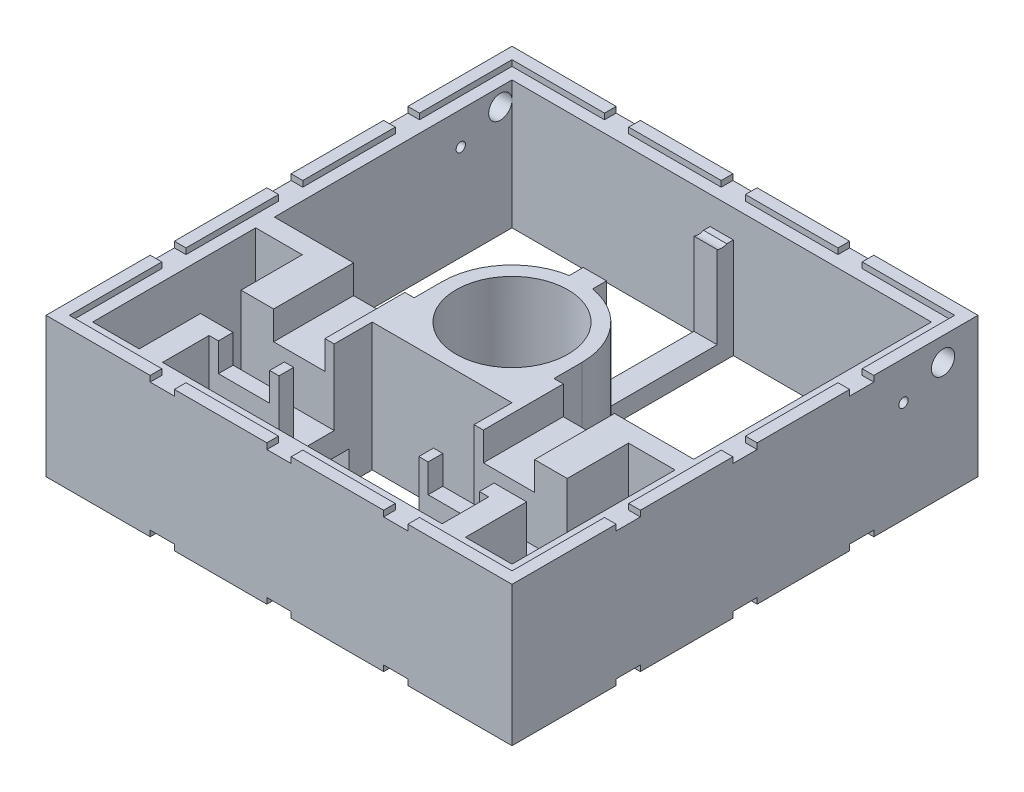
SolidWorks part; units mm, degrees
material "Polyethylene Cross-Linked"
ref_plane "Front Plane" through (0, 0, 0) normal (0, 0, 1) x (1, 0, 0)
ref_plane "Top Plane" through (0, 0, 0) normal (0, 1, 0) x (1, 0, 0)
ref_plane "Right Plane" through (0, 0, 0) normal (1, 0, 0) x (0, 0, -1)
sketch "Sketch1" plane through (0, 0, 0) normal (0, 1, 0) x (1, 0, 0)
  line L0 (57.15, 57.15) -> (-57.15, 57.15)
  line L5 (63.5, -63.5) -> (-63.5, -63.5)
  line L6 (63.5, -63.5) -> (63.5, 63.5)
  line L7 (63.5, 63.5) -> (-63.5, 63.5)
  line L8 (-63.5, -63.5) -> (-63.5, 63.5)
  line L9 (63.5, -63.5) -> (-63.5, 63.5) construction
  line L10 (63.5, 63.5) -> (-63.5, -63.5) construction
  line L11 (-57.15, -57.15) -> (-57.15, 57.15)
  line L12 (57.15, -57.15) -> (-57.15, -57.15)
  line L13 (57.15, -57.15) -> (57.15, 57.15)
  point P0 (0, 0)
  dimension "D2" = 6.35
  dimension "D1" = 127
extrude "Boss-Extrude1" add sketch "Sketch1" along normal blind 38.1
sketch "Sketch2" plane through (0, 0, 0) normal (0, 1, 0) x (1, 0, 0)
  line L0 (-57.15, -12.7) -> (-57.15, -7.62)
  line L2 (-57.15, -7.62) -> (-19.05, -7.62)
  line L3 (-19.05, -7.62) -> (-19.05, -44.45)
  line L7 (-44.45, -57.15) -> (-44.45, -12.7)
  line L8 (-44.45, -12.7) -> (-57.15, -12.7)
  line L9 (0, -76.0173) -> (0, 81.3082) construction
  line L12 (44.45, -57.15) -> (44.45, -12.7)
  line L13 (44.45, -12.7) -> (57.15, -12.7)
  line L14 (57.15, -7.62) -> (19.05, -7.62)
  line L15 (19.05, -7.62) -> (19.05, -44.45)
  line L16 (-19.05, -19.05) -> (19.05, -19.05)
  line L17 (-3.175, 57.15) -> (-3.175, 18.7836)
  line L19 (3.175, 57.15) -> (3.175, 18.7836)
  line L20 (3.175, 57.15) -> (-3.175, 57.15)
  line L21 (57.15, -7.62) -> (57.15, -12.7)
  line L24 (-19.05, -44.45) -> (-38.1, -44.45)
  line L27 (-38.1, -44.45) -> (-38.1, -57.15)
  line L28 (19.05, -44.45) -> (38.1, -44.45)
  line L29 (38.1, -44.45) -> (38.1, -57.15)
  line L30 (-19.05, 0) -> (-19.05, -7.62)
  line L31 (19.05, 0) -> (19.05, -7.62)
  line L32 (-44.45, -57.15) -> (-38.1, -57.15)
  line L33 (44.45, -57.15) -> (38.1, -57.15)
  line L34 (-57.15, -57.15) -> (57.15, -57.15) construction
  line L35 (-57.15, 57.15) -> (-57.15, -57.15) construction
  line L36 (57.15, 57.15) -> (-57.15, 57.15) construction
  circle A4 centre (0, 0) radius 19.05
  point P27 (0, -19.05)
  dimension "D5" = 6.35
  dimension "D7" = 38.1
  dimension "D1" = 44.45
  dimension "D2" = 5.08
  dimension "D3" = 12.7
  dimension "D4" = 25.4
  dimension "D6" = 6.35
  dimension "D8" = 12.7
extrude "Boss-Extrude2" add sketch "Sketch2" along normal up to surface (38.1 mm away) contours A4 L9 | L9 A4 | L9 A4 L19 L20 | A4 L9 L20 L17 | L7 L32 L27 L24 L3 L2 L0 L8 | L33 L12 L13 L21 L14 L15 L28 L29 | A4 L30 L3 L16 | A4 L16 L15 L31 region at (-33.5981, 0, 26.9354) region at (-14.7948, 0, 14.7948) region at (-8.0851, 0, 0) region at (14.7948, 0, 14.7948) region at (8.0851, 0, 0) region at (-1.5893, 0, -38.0556) region at (1.5893, 0, -38.0556) region at (33.5981, 0, 26.9354) up to face at (0, 38.1, 0)
sketch "Sketch3" plane through (88.9, 38.1, 0) normal (0, -1, 0) x (-1, 0, 0)
  circle A0 centre (88.9, 0) radius 15.24
  arc A1 (85.725, 18.7836) -> (69.85, 0) centre (88.9, 0) ccw construction
  dimension "D1" = 30.48
extrude "Cut-Extrude1" cut sketch "Sketch3" along normal offset from surface (34.29 mm away) 3.81 up to face at (50.8, 0, 34.925)
sketch "Sketch4" plane through (44.45, 0, 0) normal (1, 0, 0) x (0, 0, -1)
  line L0 (-34.925, 38.1) -> (-34.925, 0) construction
  line L3 (-40.4495, 21.59) -> (-40.4495, 16.0655)
  line L4 (-40.4495, 21.59) -> (-40.4495, 38.1)
  line L5 (-40.4495, 38.1) -> (-29.4005, 38.1)
  line L6 (-29.4005, 38.1) -> (-29.4005, 21.59)
  line L7 (-12.7, 38.1) -> (-57.15, 38.1) construction
  line L8 (-40.4495, 16.0655) -> (-29.4005, 16.0655)
  line L9 (-29.4005, 16.0655) -> (-29.4005, 21.59)
  circle A0 centre (-34.925, 21.59) radius 5.5245 construction
  dimension "D1" = 11.049
  dimension "D2" = 16.51
extrude "Cut-Extrude2" cut sketch "Sketch4" against normal up to surface (25.4 mm away) contours L4 L6 region at (44.45, 27.0828, 34.925) up to face at (19.05, 19.05, 31.75)
sketch "Sketch5" plane through (-44.45, 0, 0) normal (-1, 0, 0) x (0, 0, 1)
  line L3 (40.4495, 21.59) -> (40.4495, 38.1)
  line L4 (40.4495, 38.1) -> (29.4005, 38.1)
  line L5 (29.4005, 38.1) -> (29.4005, 21.59)
  line L6 (40.4495, 21.59) -> (40.4495, 38.1)
  line L7 (40.4495, 38.1) -> (29.4005, 38.1)
  line L8 (29.4005, 38.1) -> (29.4005, 21.59)
  line L12 (40.4495, 16.0655) -> (40.4495, 21.59)
  line L13 (40.4495, 16.0655) -> (40.4495, 21.59)
  line L14 (29.4005, 16.0655) -> (40.4495, 16.0655)
  line L15 (29.4005, 16.0655) -> (40.4495, 16.0655)
  line L16 (29.4005, 21.59) -> (29.4005, 16.0655)
  line L17 (29.4005, 21.59) -> (29.4005, 16.0655)
  dimension "D1" = 0
extrude "Cut-Extrude3" cut sketch "Sketch5" against normal up to next
sketch "Sketch8" plane through (0, 38.1, 0) normal (0, 1, 0) x (1, 0, 0)
  line L0 (-60.325, 60.325) -> (-35.1155, 60.325)
  line L1 (-35.1155, 60.325) -> (-35.1155, 63.5)
  line L2 (63.5, 63.5) -> (-63.5, 63.5) construction
  line L3 (-35.1155, 63.5) -> (-28.5115, 63.5)
  line L4 (-28.5115, 63.5) -> (-28.5115, 60.325)
  line L5 (-28.5115, 60.325) -> (-3.302, 60.325)
  line L6 (-60.325, 60.325) -> (-60.325, 35.1155)
  line L7 (-60.325, 35.1155) -> (-63.5, 35.1155)
  line L8 (-63.5, 63.5) -> (-63.5, -63.5) construction
  line L9 (-63.5, 35.1155) -> (-63.5, 28.5115)
  line L10 (-63.5, 28.5115) -> (-60.325, 28.5115)
  line L11 (-60.325, 28.5115) -> (-60.325, 3.302)
  line L12 (-60.325, 3.302) -> (-63.5, 3.302)
  line L13 (-63.5, 3.302) -> (-63.5, -3.302)
  line L14 (-63.5, -3.302) -> (-60.325, -3.302)
  line L15 (-60.325, -3.302) -> (-60.325, -28.5115)
  line L16 (-60.325, -28.5115) -> (-63.5, -28.5115)
  line L17 (-63.5, -28.5115) -> (-63.5, -35.1155)
  line L18 (-63.5, -35.1155) -> (-60.325, -35.1155)
  line L19 (-60.325, -35.1155) -> (-60.325, -60.325)
  line L20 (-60.325, -60.325) -> (-35.1155, -60.325)
  line L21 (-35.1155, -60.325) -> (-35.1155, -63.5)
  line L22 (-63.5, -63.5) -> (63.5, -63.5) construction
  line L23 (-35.1155, -63.5) -> (-28.5115, -63.5)
  line L24 (-28.5115, -63.5) -> (-28.5115, -60.325)
  line L25 (-28.5115, -60.325) -> (-3.302, -60.325)
  line L26 (-3.302, 60.325) -> (-3.302, 63.5)
  line L27 (3.302, -60.325) -> (3.302, -63.5)
  line L28 (-3.302, 63.5) -> (3.302, 63.5)
  line L29 (-3.302, -60.325) -> (-3.302, -63.5)
  line L30 (-3.302, -63.5) -> (3.302, -63.5)
  line L31 (0, 63.5) -> (0, -63.5) construction
  line L32 (28.5115, -60.325) -> (3.302, -60.325)
  line L33 (28.5115, -63.5) -> (28.5115, -60.325)
  line L34 (35.1155, -63.5) -> (28.5115, -63.5)
  line L35 (35.1155, -60.325) -> (35.1155, -63.5)
  line L36 (60.325, -60.325) -> (35.1155, -60.325)
  line L37 (60.325, -35.1155) -> (60.325, -60.325)
  line L38 (63.5, -35.1155) -> (60.325, -35.1155)
  line L39 (63.5, -28.5115) -> (63.5, -35.1155)
  line L40 (60.325, -28.5115) -> (63.5, -28.5115)
  line L41 (60.325, -3.302) -> (60.325, -28.5115)
  line L42 (63.5, -3.302) -> (60.325, -3.302)
  line L43 (63.5, 3.302) -> (63.5, -3.302)
  line L44 (60.325, 3.302) -> (63.5, 3.302)
  line L45 (60.325, 28.5115) -> (60.325, 3.302)
  line L46 (63.5, 28.5115) -> (60.325, 28.5115)
  line L47 (63.5, 35.1155) -> (63.5, 28.5115)
  line L48 (60.325, 35.1155) -> (63.5, 35.1155)
  line L49 (60.325, 60.325) -> (60.325, 35.1155)
  line L50 (60.325, 60.325) -> (35.1155, 60.325)
  line L51 (35.1155, 60.325) -> (35.1155, 63.5)
  line L52 (35.1155, 63.5) -> (28.5115, 63.5)
  line L53 (28.5115, 63.5) -> (28.5115, 60.325)
  line L54 (28.5115, 60.325) -> (3.302, 60.325)
  line L55 (3.302, 60.325) -> (3.302, 63.5)
  point P41 (-63.5, 0)
  dimension "D1" = 3.175
  dimension "D2" = 3.175
  dimension "D3" = 3.175
  dimension "D4" = 6.604
  dimension "D6" = 3.302
extrude "Cut-Extrude6" cut sketch "Sketch8" against normal blind 1.5875
sketch "Sketch9" plane through (3.175, 0, 0) normal (1, 0, 0) x (0, 0, -1)
  line L0 (22.5936, 36.5125) -> (22.5936, 6.35)
  line L1 (18.7836, 36.5125) -> (57.15, 36.5125) construction
  line L2 (22.5936, 6.35) -> (52.7561, 6.35)
  line L4 (22.5936, 36.5125) -> (53.34, 36.5125)
  line L5 (18.7836, 36.5125) -> (18.7836, 0) construction
  line L6 (57.15, 0) -> (18.7836, 0) construction
  line L7 (53.34, 36.5125) -> (57.15, 36.5125)
  line L8 (57.15, 36.5125) -> (57.15, 28.8925)
  line L9 (57.15, 28.8925) -> (52.7561, 28.8925)
  line L10 (52.7561, 28.8925) -> (52.7561, 6.35)
  point P4 (37.9668, 36.5125)
  dimension "D1" = 3.81
  dimension "D2" = 6.35
  dimension "D3" = 7.62
extrude "Cut-Extrude7" cut sketch "Sketch9" against normal up to next
sketch "Sketch10" plane through (0, 0, 7.62) normal (0, 0, -1) x (-1, 0, 0)
  line L0 (21.59, 36.5125) -> (21.59, 28.7655)
  line L1 (21.59, 28.7655) -> (35.56, 28.7655)
  line L2 (35.56, 28.7655) -> (35.56, 36.5125)
  line L3 (28.5115, 36.5125) -> (35.1155, 36.5125) construction
  line L4 (35.56, 36.5125) -> (21.59, 36.5125)
  line L5 (38.1, 36.5125) -> (38.1, 0) construction
  line L6 (19.05, 16.0655) -> (19.05, 36.5125) construction
  line L7 (19.05, 36.5125) -> (57.15, 36.5125) construction
  line L8 (19.05, 16.0655) -> (44.45, 16.0655) construction
  line L9 (0, -5.813) -> (0, 43.4051) construction
  line L10 (-21.59, 28.7655) -> (-35.56, 28.7655)
  line L11 (-35.56, 28.7655) -> (-35.56, 36.5125)
  line L12 (-35.56, 36.5125) -> (-21.59, 36.5125)
  line L13 (-21.59, 36.5125) -> (-21.59, 28.7655)
  dimension "D1" = 2.54
  dimension "D2" = 2.54
  dimension "D3" = 12.7
extrude "Cut-Extrude8" cut sketch "Sketch10" against normal up to surface (36.83 mm away) up to face at (28.575, 18.2563, 44.45)
sketch "Sketch11" plane through (0, 0, 0) normal (0, -1, 0) x (1, 0, 0)
  line L0 (0, 63.5) -> (0, -63.5) construction
  line L1 (25.4, 25.4) -> (19.05, 25.4)
  line L2 (19.05, 25.4) -> (19.05, 38.1)
  line L3 (-19.05, 38.1) -> (-38.1, 38.1)
  line L4 (-19.05, 19.05) -> (-19.05, 44.45) construction
  line L5 (-38.1, 38.1) -> (-38.1, 7.62)
  line L6 (-57.15, 7.62) -> (-19.05, 7.62) construction
  line L7 (-38.1, 7.62) -> (-25.4, 7.62)
  line L8 (-25.4, 7.62) -> (-25.4, 25.4)
  line L9 (-25.4, 25.4) -> (-19.05, 25.4)
  line L10 (-19.05, 25.4) -> (-19.05, 38.1)
  line L11 (-38.1, 44.45) -> (-38.1, 57.15) construction
  line L12 (-19.05, 44.45) -> (-38.1, 44.45) construction
  line L13 (25.4, 7.62) -> (25.4, 25.4)
  line L14 (38.1, 7.62) -> (25.4, 7.62)
  line L15 (19.05, 38.1) -> (38.1, 38.1)
  line L16 (38.1, 38.1) -> (38.1, 7.62)
  point P5 (-19.05, 31.75)
  dimension "D1" = 6.35
extrude "Cut-Extrude9" cut sketch "Sketch11" against normal blind 9.7155
extrude "Cut-Extrude10" cut sketch "Sketch8<2>" along normal blind 1.5875 from surface starting at face at (50.8, 0, 34.925)
sketch "Sketch8<2>" plane through (0, 38.1, 0) normal (0, 1, 0) x (1, 0, 0) same geometry as "Sketch8"
sketch "Sketch12" plane through (-63.5, 0, 0) normal (-1, 0, 0) x (0, 0, 1)
  line L0 (-63.5, 38.1) -> (-35.1155, 38.1) construction
  line L1 (-63.5, 38.1) -> (-63.5, 0) construction
  circle A0 centre (-53.975, 31.75) radius 3.175
  dimension "D1" = 6.35
  dimension "D2" = 6.35
  dimension "D3" = 9.525
extrude "Cut-Extrude11" cut sketch "Sketch12" against normal through all both and the other way through all
sketch "Sketch13" plane through (-63.5, 0, 0) normal (-1, 0, 0) x (0, 0, 1)
  line L0 (-63.5, 38.1) -> (-63.5, 0) construction
  line L1 (-63.5, 38.1) -> (-35.1155, 38.1) construction
  circle A0 centre (-43.18, 27.6225) radius 1.27
  dimension "D3" = 2.54
  dimension "D1" = 20.32
  dimension "D2" = 10.4775
extrude "Cut-Extrude12" cut sketch "Sketch13" against normal up to next
extrude "Cut-Extrude13" cut sketch "Sketch13<2>" along normal blind 3.175 from surface starting at face at (63.5, 31.75, -50.8)
sketch "Sketch13<2>" plane through (-63.5, 0, 0) normal (-1, 0, 0) x (0, 0, 1) same geometry as "Sketch13"
sketch "Sketch14" plane through (0, 1.5875, 0) normal (0, -1, 0) x (1, 0, 0)
  line L0 (0, 0) -> (-14.5497, -12.2967) construction
  line L1 (-18.7488, -3.3744) -> (-14.8782, -0.1032)
  line L2 (-6.452, -17.9241) -> (-2.5814, -14.6529)
  line L3 (-14.8782, -0.1032) -> (-2.5814, -14.6529)
  arc A0 (-18.7488, -3.3744) -> (-6.452, -17.9241) centre (0, 0) ccw
  arc A2 (-19.05, 0) -> (-3.175, -18.7836) centre (0, 0) ccw construction
  point P7 (-14.1755, -2.4355)
  point P9 (-14.5497, -12.2967)
  dimension "D1" = 60
  dimension "D2" = 7.62
extrude "Cut-Extrude14" cut sketch "Sketch14" against normal offset from surface (11.7475 mm away) 9.525 up to face at (0, 3.81, 15.24) offset beyond the face yes
